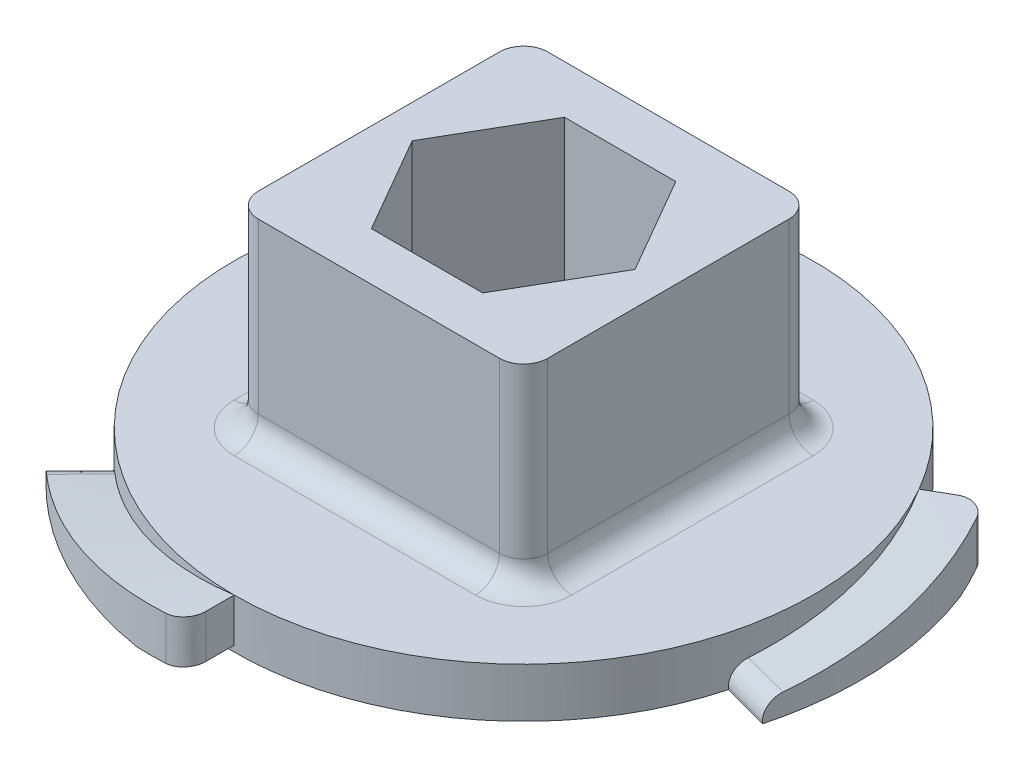
SolidWorks part; units mm, degrees
material "Nylon 6/10"
ref_plane "Front Plane" through (0, 0, 0) normal (0, 0, 1) x (1, 0, 0)
ref_plane "Top Plane" through (0, 0, 0) normal (0, 1, 0) x (1, 0, 0)
ref_plane "Right Plane" through (0, 0, 0) normal (1, 0, 0) x (0, 0, -1)
sketch "Sketch1" plane through (0, 0, 0) normal (0, 1, 0) x (1, 0, 0)
  circle A0 centre (0, 0) radius 6
  dimension "D1" = 12
extrude "Boss-Extrude1" add sketch "Sketch1" along normal blind 0.55
sketch "Sketch2" plane through (0, 0.55, 0) normal (0, 1, 0) x (1, 0, 0)
  line L0 (0.5, 5.4772) -> (0.5, 4.3463)
  line L1 (-0.5, 5.4772) -> (-0.5, 4.3463)
  line L2 (5.4772, 0.5) -> (4.3463, 0.5)
  line L3 (5.4772, -0.5) -> (4.3463, -0.5)
  line L4 (-0.5, 5.4772) -> (0.5, 5.4772) construction
  line L5 (0, -3.3847) -> (0, 3.3847) construction
  line L6 (5.4772, 0.5) -> (5.4772, -0.5) construction
  line L7 (-3.3847, 0) -> (3.3847, 0) construction
  line L8 (-4.3463, -0.5) -> (-5.4772, -0.5)
  line L9 (-0.5, -4.3463) -> (-0.5, -5.4772)
  line L10 (0.5, -4.3463) -> (0.5, -5.4772)
  line L11 (-4.3463, 0.5) -> (-5.4772, 0.5)
  arc A0 (5.4772, 0.5) -> (0.5, 5.4772) centre (0, 0) ccw
  arc A1 (4.3463, 0.5) -> (0.5, 4.3463) centre (0, 0) ccw
  arc A2 (-4.3463, -0.5) -> (-0.5, -4.3463) centre (0, 0) ccw
  arc A3 (-5.4772, -0.5) -> (-0.5, -5.4772) centre (0, 0) ccw
  arc A4 (0.5, -5.4772) -> (5.4772, -0.5) centre (0, 0) ccw
  arc A5 (0.5, -4.3463) -> (4.3463, -0.5) centre (0, 0) ccw
  arc A6 (-0.5, 4.3463) -> (-4.3463, 0.5) centre (0, 0) ccw
  arc A7 (-0.5, 5.4772) -> (-5.4772, 0.5) centre (0, 0) ccw
  point P12 (0, 5.4772)
  point P15 (5.4772, 0)
  dimension "D1" = 11
  dimension "D2" = 8.75
  dimension "D3" = 1
  dimension "D4" = 1
sketch "Sketch3" plane through (0, 0.55, 0) normal (0, 1, 0) x (1, 0, 0)
  line L0 (0, 0) -> (0, 6)
  line L1 (0, -3.3847) -> (0, 3.3847) construction
  line L2 (0, 0) -> (0, -6)
  circle A0 centre (0, 0) radius 6 construction
ref_point "Point1"
ref_point "Point2"
sketch "Sketch4" plane through (0, 0, 0) normal (0, -1, 0) x (1, 0, 0)
  circle A0 centre (0, 0) radius 6 construction
  circle A1 centre (0, 0) radius 6
curve "Helix/Spiral1" pitch 5 height 0.625 radius 6 centre (0, 0, 0) axis (0, -1, 0) start towards (0, 0, 1)
sketch "Sketch5" plane through (0, 0, 0) normal (1, 0, 0) x (0, 0, -1)
  line L1 (-6, -0.35) -> (-7, -0.35)
  line L2 (-6, -0.35) -> (-6, 0.55)
  line L3 (-6, 0.55) -> (-7, 0.55)
  line L4 (-7, -0.35) -> (-7, 0.55)
  line L5 (-6, -0.35) -> (-7, 0.55) construction
  line L6 (-6, 0.55) -> (-7, -0.35) construction
  point P4 (-6.5, 0.1)
  dimension "D1" = 0.9
  dimension "D2" = 1
sweep "Sweep1" add profiles "Sketch5" path "Helix/Spiral1"
ref_axis "Axis1" through (0, 0.55, 0) along (0, -1, 0)
pattern_circular "CirPattern1" count 3 over 360 about axis through (0, 0.55, 0) along (0, -1, 0) of "Sweep1"
sketch "Sketch6" plane through (0, 0.55, 0) normal (0, 1, 0) x (1, 0, 0)
  circle A0 centre (0, 0) radius 6
  circle A1 centre (0, 0) radius 6 construction
extrude "Cut-Extrude1" [suppressed] cut sketch "Sketch6" along normal through all
sketch "Sketch7" plane through (0, 0.55, 0) normal (0, 1, 0) x (1, 0, 0)
  line L1 (-3, -3) -> (3, -3)
  line L2 (-3, -3) -> (-3, 3)
  line L3 (-3, 3) -> (3, 3)
  line L4 (3, -3) -> (3, 3)
  line L5 (-3, -3) -> (3, 3) construction
  line L6 (-3, 3) -> (3, -3) construction
  point P0 (0, 0)
  dimension "D1" = 6
  dimension "D2" = 6
extrude "Boss-Extrude2" add sketch "Sketch7" along normal blind 4
sketch "Sketch8" plane through (0, 0, 0) normal (0, -1, 0) x (1, 0, 0)
  circle A1 centre (0, 0) radius 6
  circle A2 centre (0, 0) radius 5
  arc A3 (5.1962, -3) -> (-3.8289, 4.6195) centre (0, 0) ccw construction
  dimension "D1" = 1
extrude "Boss-Extrude3" add sketch "Sketch8" along normal up to vertex (0.975 mm away) up to point (-4.2426, -0.975, 4.2426)
sketch "Sketch10" plane through (0, -0.975, 0) normal (0, -1, 0) x (1, 0, 0)
  circle A0 centre (0, 0) radius 7.381
extrude "Cut-Extrude3" cut sketch "Sketch10" against normal blind 0.5
fillet "Fillet2" radius 0.4 6 edges at (0, 0.1, 7) (-6.0622, 0.1, -3.5) (6.0622, 0.1, -3.5)
sketch "Sketch11" plane through (0, 4.55, 0) normal (0, 1, 0) x (1, 0, 0)
  line L0 (-3, -3) -> (3, -3) construction
  line L1 (-1.1547, -2) -> (1.1547, -2)
  line L2 (1.1547, -2) -> (2.3094, 0)
  line L3 (2.3094, 0) -> (1.1547, 2)
  line L4 (1.1547, 2) -> (-1.1547, 2)
  line L5 (-1.1547, 2) -> (-2.3094, 0)
  line L6 (-2.3094, 0) -> (-1.1547, -2)
  circle A0 centre (0, 0) radius 2 construction
  dimension "D1" = 4
extrude "Cut-Extrude4" cut sketch "Sketch11" against normal blind 4
fillet "Fillet3" radius 0.5 8 edges at (3, 2.55, 3) (3, 2.55, -3) (-3, 2.55, -3) (-3, 2.55, 3) (-3, 0.55, 0) (0, 0.55, 3) (0, 0.55, -3) (3, 0.55, 0)
sketch "Sketch12" plane through (0, 0.55, 0) normal (0, 1, 0) x (1, 0, 0)
  circle A0 centre (0, 0) radius 1.5
  dimension "D1" = 3
extrude "Cut-Extrude5" [suppressed] cut sketch "Sketch12" against normal through all
